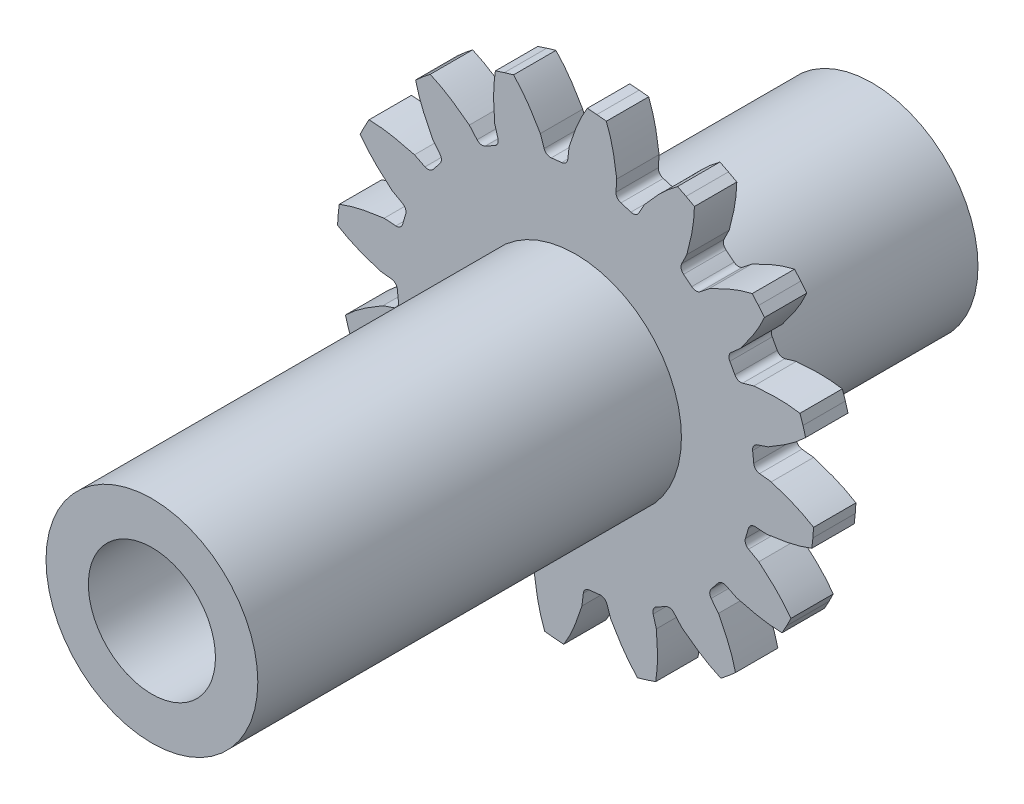
SolidWorks part; units mm, degrees
ref_plane "Front Plane" through (0, 0, 0) normal (0, 0, 1) x (1, 0, 0)
ref_plane "Top Plane" through (0, 0, 0) normal (0, 1, 0) x (1, 0, 0)
ref_plane "Right Plane" through (0, 0, 0) normal (1, 0, 0) x (0, 0, -1)
sketch "Sketch1" plane through (0, 0, 0) normal (0, 0, 1) x (1, 0, 0)
  circle A0 centre (0, 0) radius 10
  circle A1 centre (0, 0) radius 8.4375
  circle A2 centre (0, 0) radius 11.25
  circle A3 centre (0, 0) radius 8.5925
  circle A4 centre (0, 0) radius 100
sketch "Sketch2" plane through (0, 0, 0) normal (0, 0, 1) x (1, 0, 0)
  line L0 (0, 0) -> (0, 16.2403) construction
  line L1 (0, 0) -> (3.8268, 9.2388) construction
  line L2 (3.8268, 9.2388) -> (6.4557, 15.5853) construction
  line L3 (-0.3026, 9.2388) -> (-0.3962, 8.4282)
  line L4 (0, 0) -> (1.0067, 11.2049) construction
  line L5 (1.9446, 9.0369) -> (1.8922, 8.2226)
  line L6 (3.2559, 8.6513) -> (2.8592, 7.9383)
  line L7 (0, 0) -> (5.218, 9.9667) construction
  line L8 (5.2548, 7.6048) -> (4.8948, 6.8726)
  line L9 (6.3188, 6.7468) -> (5.6794, 6.2398)
  line L10 (7.7651, 5.015) -> (7.1522, 4.4762)
  line L11 (8.4197, 3.8151) -> (7.635, 3.5914)
  line L12 (9.0932, 1.6617) -> (8.3208, 1.3985)
  line L13 (9.2388, 0.3026) -> (8.4282, 0.3962)
  line L14 (9.0369, -1.9446) -> (8.2226, -1.8922)
  line L15 (8.6513, -3.2559) -> (7.9383, -2.8592)
  line L16 (7.6048, -5.2548) -> (6.8726, -4.8948)
  line L17 (6.7468, -6.3188) -> (6.2398, -5.6794)
  line L18 (5.015, -7.7651) -> (4.4762, -7.1522)
  line L19 (3.8151, -8.4197) -> (3.5914, -7.635)
  line L20 (1.6617, -9.0932) -> (1.3985, -8.3208)
  line L21 (0.3026, -9.2388) -> (0.3962, -8.4282)
  line L22 (-1.9446, -9.0369) -> (-1.8922, -8.2226)
  line L23 (-3.2559, -8.6513) -> (-2.8592, -7.9383)
  line L24 (-5.2548, -7.6048) -> (-4.8948, -6.8726)
  line L25 (-6.3188, -6.7468) -> (-5.6794, -6.2398)
  line L26 (-7.7651, -5.015) -> (-7.1522, -4.4762)
  line L27 (-8.4197, -3.8151) -> (-7.635, -3.5914)
  line L28 (-9.0932, -1.6617) -> (-8.3208, -1.3985)
  line L29 (-9.2388, -0.3026) -> (-8.4282, -0.3962)
  line L30 (-9.0369, 1.9446) -> (-8.2226, 1.8922)
  line L31 (-8.6513, 3.2559) -> (-7.9383, 2.8592)
  line L32 (-7.6048, 5.2548) -> (-6.8726, 4.8948)
  line L33 (-6.7468, 6.3188) -> (-6.2398, 5.6794)
  line L34 (-5.015, 7.7651) -> (-4.4762, 7.1522)
  line L35 (-3.8151, 8.4197) -> (-3.5914, 7.635)
  line L36 (-1.6617, 9.0932) -> (-1.3985, 8.3208)
  arc A0 (0, 10) -> (3.8268, 9.2388) centre (0, 0) cw
  circle A1 centre (0, 0) radius 10 construction
  circle A2 centre (0, 0) radius 11.25 construction
  circle A3 centre (0, 0) radius 8.4375 construction
  spline S0 degree 3 poles (-0.3026, 9.2388) (-0.0851, 9.9279) (0.1696, 10.6213) (0.5574, 11.2362) knots 0 0 0 0 1 1 1 1
  spline S1 degree 1 poles (0.5574, 11.2362) (1.0067, 11.2049) knots 0 0 1 1
  spline S2 degree 3 poles (1.9446, 9.0369) (1.8533, 9.7537) (1.7263, 10.4814) (1.4544, 11.1556) knots 0 0 0 0 1 1 1 1
  spline S3 degree 1 poles (1.4544, 11.1556) (1.0067, 11.2049) knots 0 0 1 1
  spline S4 degree 3 poles (3.2559, 8.6513) (3.721, 9.2044) (4.2213, 9.7479) (4.8148, 10.1676) knots 0 0 0 0 1 1 1 1
  spline S5 degree 1 poles (4.8148, 10.1676) (5.218, 9.9667) knots 0 0 1 1
  spline S6 degree 1 poles (5.6127, 9.7499) (5.218, 9.9667) knots 0 0 1 1
  spline S7 degree 3 poles (5.2548, 7.6048) (5.4443, 8.3021) (5.606, 9.0229) (5.6127, 9.7499) knots 0 0 0 0 1 1 1 1
  spline S8 degree 2 poles (1.8922, 8.2226) (2.3842, 8.1093) (2.8592, 7.9383) knots 0 0 0 1 1 1
  spline S9 degree 2 poles (4.8948, 6.8726) (5.306, 6.5797) (5.6794, 6.2398) knots 0 0 0 1 1 1
  spline S10 degree 3 poles (6.3188, 6.7468) (6.9599, 7.0802) (7.6303, 7.3904) (8.3393, 7.5511) knots 0 0 0 0 1 1 1 1
  spline S11 degree 1 poles (8.3393, 7.5511) (8.6349, 7.2112) knots 0 0 1 1
  spline S12 degree 1 poles (8.9166, 6.8598) (8.6349, 7.2112) knots 0 0 1 1
  spline S13 degree 3 poles (7.7651, 5.015) (8.2074, 5.5864) (8.6322, 6.1908) (8.9166, 6.8598) knots 0 0 0 0 1 1 1 1
  spline S14 degree 2 poles (7.1522, 4.4762) (7.4201, 4.0483) (7.635, 3.5914) knots 0 0 0 1 1 1
  spline S15 degree 3 poles (8.4197, 3.8151) (9.1396, 3.8773) (9.8777, 3.9079) (10.5942, 3.785) knots 0 0 0 0 1 1 1 1
  spline S16 degree 1 poles (10.5942, 3.785) (10.7372, 3.3579) knots 0 0 1 1
  spline S17 degree 1 poles (10.863, 2.9254) (10.7372, 3.3579) knots 0 0 1 1
  spline S18 degree 3 poles (9.0932, 1.6617) (9.7202, 2.0208) (10.3442, 2.4161) (10.863, 2.9254) knots 0 0 0 0 1 1 1 1
  spline S19 degree 2 poles (8.3208, 1.3985) (8.4044, 0.9007) (8.4282, 0.3962) knots 0 0 0 1 1 1
  spline S20 degree 3 poles (9.2388, 0.3026) (9.9279, 0.0851) (10.6213, -0.1696) (11.2362, -0.5574) knots 0 0 0 0 1 1 1 1
  spline S21 degree 1 poles (11.2362, -0.5574) (11.2049, -1.0067) knots 0 0 1 1
  spline S22 degree 1 poles (11.1556, -1.4544) (11.2049, -1.0067) knots 0 0 1 1
  spline S23 degree 3 poles (9.0369, -1.9446) (9.7537, -1.8533) (10.4814, -1.7263) (11.1556, -1.4544) knots 0 0 0 0 1 1 1 1
  spline S24 degree 2 poles (8.2226, -1.8922) (8.1093, -2.3842) (7.9383, -2.8592) knots 0 0 0 1 1 1
  spline S25 degree 3 poles (8.6513, -3.2559) (9.2044, -3.721) (9.7479, -4.2213) (10.1676, -4.8148) knots 0 0 0 0 1 1 1 1
  spline S26 degree 1 poles (10.1676, -4.8148) (9.9667, -5.218) knots 0 0 1 1
  spline S27 degree 1 poles (9.7499, -5.6127) (9.9667, -5.218) knots 0 0 1 1
  spline S28 degree 3 poles (7.6048, -5.2548) (8.3021, -5.4443) (9.0229, -5.606) (9.7499, -5.6127) knots 0 0 0 0 1 1 1 1
  spline S29 degree 2 poles (6.8726, -4.8948) (6.5797, -5.306) (6.2398, -5.6794) knots 0 0 0 1 1 1
  spline S30 degree 3 poles (6.7468, -6.3188) (7.0802, -6.9599) (7.3904, -7.6303) (7.5511, -8.3393) knots 0 0 0 0 1 1 1 1
  spline S31 degree 1 poles (7.5511, -8.3393) (7.2112, -8.6349) knots 0 0 1 1
  spline S32 degree 1 poles (6.8598, -8.9166) (7.2112, -8.6349) knots 0 0 1 1
  spline S33 degree 3 poles (5.015, -7.7651) (5.5864, -8.2074) (6.1908, -8.6322) (6.8598, -8.9166) knots 0 0 0 0 1 1 1 1
  spline S34 degree 2 poles (4.4762, -7.1522) (4.0483, -7.4201) (3.5914, -7.635) knots 0 0 0 1 1 1
  spline S35 degree 3 poles (3.8151, -8.4197) (3.8773, -9.1396) (3.9079, -9.8777) (3.785, -10.5942) knots 0 0 0 0 1 1 1 1
  spline S36 degree 1 poles (3.785, -10.5942) (3.3579, -10.7372) knots 0 0 1 1
  spline S37 degree 1 poles (2.9254, -10.863) (3.3579, -10.7372) knots 0 0 1 1
  spline S38 degree 3 poles (1.6617, -9.0932) (2.0208, -9.7202) (2.4161, -10.3442) (2.9254, -10.863) knots 0 0 0 0 1 1 1 1
  spline S39 degree 2 poles (1.3985, -8.3208) (0.9007, -8.4044) (0.3962, -8.4282) knots 0 0 0 1 1 1
  spline S40 degree 3 poles (0.3026, -9.2388) (0.0851, -9.9279) (-0.1696, -10.6213) (-0.5574, -11.2362) knots 0 0 0 0 1 1 1 1
  spline S41 degree 1 poles (-0.5574, -11.2362) (-1.0067, -11.2049) knots 0 0 1 1
  spline S42 degree 1 poles (-1.4544, -11.1556) (-1.0067, -11.2049) knots 0 0 1 1
  spline S43 degree 3 poles (-1.9446, -9.0369) (-1.8533, -9.7537) (-1.7263, -10.4814) (-1.4544, -11.1556) knots 0 0 0 0 1 1 1 1
  spline S44 degree 2 poles (-1.8922, -8.2226) (-2.3842, -8.1093) (-2.8592, -7.9383) knots 0 0 0 1 1 1
  spline S45 degree 3 poles (-3.2559, -8.6513) (-3.721, -9.2044) (-4.2213, -9.7479) (-4.8148, -10.1676) knots 0 0 0 0 1 1 1 1
  spline S46 degree 1 poles (-4.8148, -10.1676) (-5.218, -9.9667) knots 0 0 1 1
  spline S47 degree 1 poles (-5.6127, -9.7499) (-5.218, -9.9667) knots 0 0 1 1
  spline S48 degree 3 poles (-5.2548, -7.6048) (-5.4443, -8.3021) (-5.606, -9.0229) (-5.6127, -9.7499) knots 0 0 0 0 1 1 1 1
  spline S49 degree 2 poles (-4.8948, -6.8726) (-5.306, -6.5797) (-5.6794, -6.2398) knots 0 0 0 1 1 1
  spline S50 degree 3 poles (-6.3188, -6.7468) (-6.9599, -7.0802) (-7.6303, -7.3904) (-8.3393, -7.5511) knots 0 0 0 0 1 1 1 1
  spline S51 degree 1 poles (-8.3393, -7.5511) (-8.6349, -7.2112) knots 0 0 1 1
  spline S52 degree 1 poles (-8.9166, -6.8598) (-8.6349, -7.2112) knots 0 0 1 1
  spline S53 degree 3 poles (-7.7651, -5.015) (-8.2074, -5.5864) (-8.6322, -6.1908) (-8.9166, -6.8598) knots 0 0 0 0 1 1 1 1
  spline S54 degree 2 poles (-7.1522, -4.4762) (-7.4201, -4.0483) (-7.635, -3.5914) knots 0 0 0 1 1 1
  spline S55 degree 3 poles (-8.4197, -3.8151) (-9.1396, -3.8773) (-9.8777, -3.9079) (-10.5942, -3.785) knots 0 0 0 0 1 1 1 1
  spline S56 degree 1 poles (-10.5942, -3.785) (-10.7372, -3.3579) knots 0 0 1 1
  spline S57 degree 1 poles (-10.863, -2.9254) (-10.7372, -3.3579) knots 0 0 1 1
  spline S58 degree 3 poles (-9.0932, -1.6617) (-9.7202, -2.0208) (-10.3442, -2.4161) (-10.863, -2.9254) knots 0 0 0 0 1 1 1 1
  spline S59 degree 2 poles (-8.3208, -1.3985) (-8.4044, -0.9007) (-8.4282, -0.3962) knots 0 0 0 1 1 1
  spline S60 degree 3 poles (-9.2388, -0.3026) (-9.9279, -0.0851) (-10.6213, 0.1696) (-11.2362, 0.5574) knots 0 0 0 0 1 1 1 1
  spline S61 degree 1 poles (-11.2362, 0.5574) (-11.2049, 1.0067) knots 0 0 1 1
  spline S62 degree 1 poles (-11.1556, 1.4544) (-11.2049, 1.0067) knots 0 0 1 1
  spline S63 degree 3 poles (-9.0369, 1.9446) (-9.7537, 1.8533) (-10.4814, 1.7263) (-11.1556, 1.4544) knots 0 0 0 0 1 1 1 1
  spline S64 degree 2 poles (-8.2226, 1.8922) (-8.1093, 2.3842) (-7.9383, 2.8592) knots 0 0 0 1 1 1
  spline S65 degree 3 poles (-8.6513, 3.2559) (-9.2044, 3.721) (-9.7479, 4.2213) (-10.1676, 4.8148) knots 0 0 0 0 1 1 1 1
  spline S66 degree 1 poles (-10.1676, 4.8148) (-9.9667, 5.218) knots 0 0 1 1
  spline S67 degree 1 poles (-9.7499, 5.6127) (-9.9667, 5.218) knots 0 0 1 1
  spline S68 degree 3 poles (-7.6048, 5.2548) (-8.3021, 5.4443) (-9.0229, 5.606) (-9.7499, 5.6127) knots 0 0 0 0 1 1 1 1
  spline S69 degree 2 poles (-6.8726, 4.8948) (-6.5797, 5.306) (-6.2398, 5.6794) knots 0 0 0 1 1 1
  spline S70 degree 3 poles (-6.7468, 6.3188) (-7.0802, 6.9599) (-7.3904, 7.6303) (-7.5511, 8.3393) knots 0 0 0 0 1 1 1 1
  spline S71 degree 1 poles (-7.5511, 8.3393) (-7.2112, 8.6349) knots 0 0 1 1
  spline S72 degree 1 poles (-6.8598, 8.9166) (-7.2112, 8.6349) knots 0 0 1 1
  spline S73 degree 3 poles (-5.015, 7.7651) (-5.5864, 8.2074) (-6.1908, 8.6322) (-6.8598, 8.9166) knots 0 0 0 0 1 1 1 1
  spline S74 degree 2 poles (-4.4762, 7.1522) (-4.0483, 7.4201) (-3.5914, 7.635) knots 0 0 0 1 1 1
  spline S75 degree 3 poles (-3.8151, 8.4197) (-3.8773, 9.1396) (-3.9079, 9.8777) (-3.785, 10.5942) knots 0 0 0 0 1 1 1 1
  spline S76 degree 1 poles (-3.785, 10.5942) (-3.3579, 10.7372) knots 0 0 1 1
  spline S77 degree 1 poles (-2.9254, 10.863) (-3.3579, 10.7372) knots 0 0 1 1
  spline S78 degree 3 poles (-1.6617, 9.0932) (-2.0208, 9.7202) (-2.4161, 10.3442) (-2.9254, 10.863) knots 0 0 0 0 1 1 1 1
  spline S79 degree 2 poles (-1.3985, 8.3208) (-0.9007, 8.4044) (-0.3962, 8.4282) knots 0 0 0 1 1 1
  point P215 (0, 0)
  dimension "D1" = 3.927
  dimension "D2" = 0.5574
  dimension "D3" = 0.5574
  dimension "D4" = 0.4476
  dimension "D5" = 0.4476
  dimension "D6" = 11.0632
  dimension "D7" = 11.0632
  dimension "D8" = 0.183
  dimension "D9" = 0.183
  dimension "D10" = 10.332
  dimension "D11" = 10.332
  dimension "D12" = 0.3026
  dimension "D13" = 0.3026
  dimension "D14" = 9.2438
  dimension "D15" = 9.2438
  dimension "D16" = 0.3962
  dimension "D17" = 0.3962
  dimension "D18" = 0.4504
  dimension "D19" = 0.4504
  dimension "D20" = 1.008
  dimension "D21" = 1.008
  dimension "D22" = 8
extrude "Boss-Extrude1" add sketch "Sketch2" along normal mid plane 20 contours L3 S79 L36 S78 S77 S76 S75 L35 S74 L34 S73 S72 S71 S70 L33 S69 L32 S68 S67 S66 S65 L31 S64 L30 S63 S62 S61 S60 L29 S59 L28 S58 S57 S56 S55 L27 S54 L26 S53 S52 S51 S50 L25 S49 L24 S48 S47 S46 S45 L23 S44 L22 S43 S42 S41 S40 L21 S39 L20 S38 S37 S36 S35 L19 S34 L18 S33 S32 S31 S30 L17 S29 L16 S28 S27 S26 S25 L15 S24 L14 S23 S22 S21 S20 L13 S19 L12 S18 S17 S16 S15 L11 S14 L10 S13 S12 S11 S10 L9 S9 L8 S7 S6 S5 S4 L6 S8 L5 S2 S3 S1 S0
ref_plane "Plane1" through (0, 0, 50) normal (0, 0, 1) x (1, 0, 0)
sketch "Sketch3" plane through (0, 0, 50) normal (0, 0, 1) x (1, 0, 0)
  circle A0 centre (0, 0) radius 12
fillet "Fillet1" radius 0.3125 32 edges at (-0.3962, 8.4282, 0) (-1.3985, 8.3208, 0) (-3.5914, 7.635, 0) (-4.4762, 7.1522, 0) (-6.2398, 5.6794, 0) (-6.8726, 4.8948, 0) (-7.9383, 2.8592, 0) (-8.2226, 1.8922, 0) (-8.4282, -0.3962, 0) (-8.3208, -1.3985, 0) (-7.635, -3.5914, 0) (-7.1522, -4.4762, 0) (-5.6794, -6.2398, 0) (-4.8948, -6.8726, 0) (-2.8592, -7.9383, 0) (-1.8922, -8.2226, 0) (0.3962, -8.4282, 0) (1.3985, -8.3208, 0) (3.5914, -7.635, 0) (4.4762, -7.1522, 0) (6.2398, -5.6794, 0) (6.8726, -4.8948, 0) (7.9383, -2.8592, 0) (8.2226, -1.8922, 0) (8.4282, 0.3962, 0) (8.3208, 1.3985, 0) (7.635, 3.5914, 0) (7.1522, 4.4762, 0) (4.8948, 6.8726, 0) (5.6794, 6.2398, 0) (1.8922, 8.2226, 0) (2.8592, 7.9383, 0)
ref_plane "Plane2" through (0, 0, 15) normal (0, 0, 1) x (1, 0, 0)
sketch "Sketch4" plane through (0, 0, 15) normal (0, 0, 1) x (1, 0, 0)
  circle A0 centre (0, 0) radius 12
sketch "Sketch5" plane through (0, 0, 10) normal (0, 0, 1) x (1, 0, 0)
  circle A0 centre (0, 0) radius 50
sketch "Sketch6" plane through (0, 0, 0) normal (1, 0, 0) x (0, 0, -1)
  line L0 (-15, 0) -> (-10, 0)
  line L1 (-15, 12) -> (-15, -12) construction
  line L2 (-10, 50) -> (-10, -50) construction
scale "Scale1" scale about origin uniform scaling no x scale factor 10 y scale factor 10 z scale factor 1
extrude "Boss-Extrude2" add sketch "Sketch5" along normal blind 200 contours A0
sketch "Sketch15" plane through (0, 0, 210) normal (0, 0, 1) x (1, 0, 0)
  circle A0 centre (0, 0) radius 30
extrude "Cut-Extrude1" cut sketch "Sketch15" against normal blind 200
sketch "Sketch16" plane through (0, 0, -10) normal (0, 0, -1) x (-1, 0, 0)
  circle A0 centre (0, 0) radius 50
extrude "Boss-Extrude3" add sketch "Sketch16" along normal blind 120
